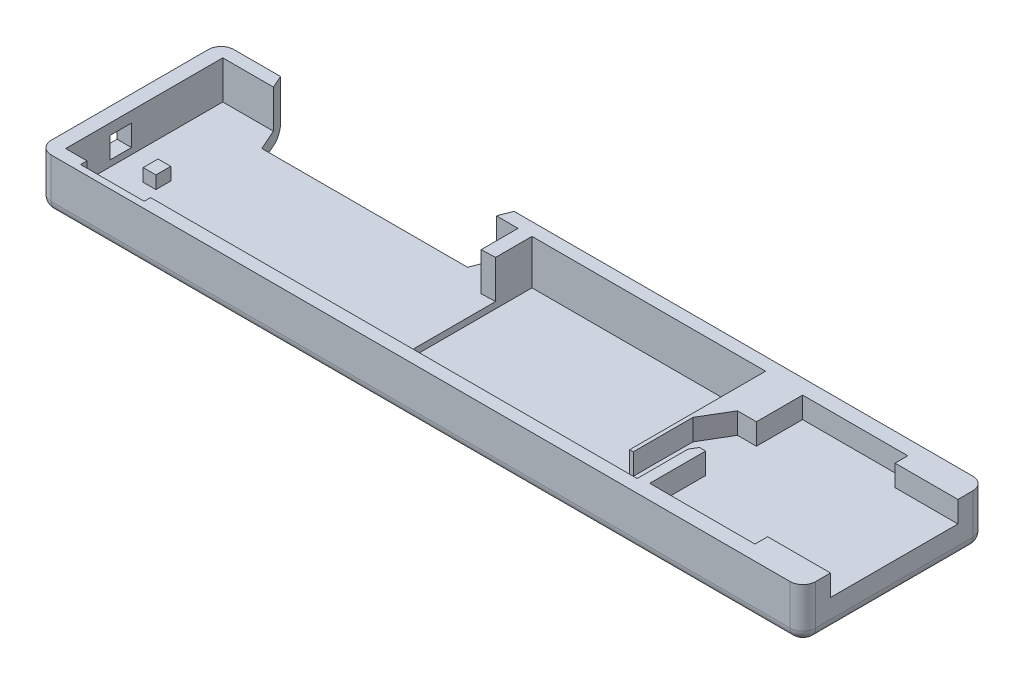
SolidWorks part; units mm, degrees
ref_plane "前视基准面" through (0, 0, 0) normal (0, 0, 1) x (1, 0, 0)
ref_plane "上视基准面" through (0, 0, 0) normal (0, 1, 0) x (1, 0, 0)
ref_plane "右视基准面" through (0, 0, 0) normal (1, 0, 0) x (0, 0, -1)
sketch "草图3" plane through (0, 0, 0) normal (0, 1, 0) x (1, 0, 0)
  line L1 (-39.9314, 29.2531) -> (140.0686, 29.2531)
  line L2 (-39.9314, 29.2531) -> (-39.9314, -13.7469)
  line L3 (-39.9314, -13.7469) -> (140.0686, -13.7469)
  line L4 (140.0686, 29.2531) -> (140.0686, -13.7469)
extrude "凸台-拉伸1" add sketch "草图3" along normal blind 12
sketch "草图4" plane through (0, 0, 0) normal (0, 1, 0) x (1, 0, 0)
  line L0 (-22.4696, -5.8589) -> (26.0023, -5.8589)
  line L1 (-39.9314, -13.7469) -> (140.0686, -13.7469) construction
  line L2 (-25.9314, -13.7469) -> (29.0686, -13.7469)
  line L5 (-25.9314, -13.7469) -> (-22.4696, -5.8589)
  line L6 (29.0686, -13.7469) -> (26.0023, -5.8589)
  point P11 (-22.4696, -5.8589)
  point P12 (26.0023, -5.8589)
extrude "切除-拉伸1" cut sketch "草图4" along normal blind 52
sketch "草图5" plane through (0, 12, 0) normal (0, 1, 0) x (1, 0, 0)
  line L6 (140.0686, -13.7469) -> (140.0686, 29.2531) construction
  line L7 (140.0686, 7.7531) -> (140.0686, 22.7531)
  line L8 (140.0686, 7.7531) -> (140.0686, -7.2469)
  line L9 (140.0686, 22.7531) -> (125.2765, 22.7531)
  line L10 (125.2765, 22.7531) -> (125.2765, -7.2469)
  line L11 (125.2765, -7.2469) -> (140.0686, -7.2469)
  point P0 (140.0686, 7.7531)
extrude "切除-拉伸2" cut sketch "草图5" against normal blind 5
sketch "草图7" plane through (0, 12, 0) normal (0, 1, 0) x (1, 0, 0)
  line L0 (125.2765, 22.7531) -> (125.2765, -7.2469) construction
  line L1 (125.2765, 7.7531) -> (125.2765, 25.7531)
  line L2 (125.2765, 7.7531) -> (125.2765, -10.2469)
  line L3 (125.2765, -10.2469) -> (100.5008, -10.2469)
  line L4 (100.5008, -10.2469) -> (100.5008, 25.7531)
  line L5 (100.5008, 25.7531) -> (125.2765, 25.7531)
  point P0 (125.2765, 7.7531)
extrude "切除-拉伸3" cut sketch "草图7" against normal blind 5
sketch "草图8" plane through (0, 12, 0) normal (0, 1, 0) x (1, 0, 0)
  line L1 (36.2763, 26.2531) -> (91.2763, 26.2531)
  line L2 (36.2763, 26.2531) -> (36.2763, -10.7469)
  line L3 (36.2763, -10.7469) -> (91.2763, -10.7469)
  line L4 (91.2763, 26.2531) -> (91.2763, -10.7469)
  line L6 (140.0686, 29.2531) -> (-39.9314, 29.2531) construction
  line L7 (29.0686, -13.7469) -> (140.0686, -13.7469) construction
  dimension "D1" = 3
  dimension "D2" = 3
extrude "切除-拉伸4" cut sketch "草图8" against normal blind 10.5
sketch "草图9" plane through (0, 12, 0) normal (0, 1, 0) x (1, 0, 0)
  line L0 (91.2763, -10.7469) -> (91.2763, 26.2531) construction
  line L1 (91.2763, 26.2531) -> (98.0396, 26.2531)
  line L2 (91.2763, 26.2531) -> (91.2763, 21.2551)
  line L4 (98.0396, 26.2531) -> (98.0396, 22.1306)
  line L5 (100.5008, 25.7531) -> (100.5008, -10.2469) construction
  line L7 (92.1327, 21.2551) -> (92.1327, 7.2269)
  line L12 (96.0473, 0.6296) -> (100.5008, 0.6296)
  line L13 (100.5008, 12.5794) -> (100.5008, 0.6296)
  line L14 (92.1327, 7.2269) -> (96.0473, 0.6296)
  line L15 (98.0396, 14.2797) -> (99.0486, 12.5794)
  line L17 (99.0486, 12.5794) -> (100.5008, 12.5794)
  line L19 (98.0396, 14.2797) -> (98.0396, 22.1306)
  line L20 (92.1327, 21.2551) -> (91.2763, 21.2551)
extrude "切除-拉伸5" cut sketch "草图9" against normal blind 5
sketch "草图10" plane through (0, 12, 0) normal (0, 1, 0) x (1, 0, 0)
  line L4 (-29.1302, -10.7469) -> (32.9986, -10.7469)
  line L5 (-29.1302, -10.7469) -> (-29.1302, -2.0631)
  line L6 (-29.1302, -2.0631) -> (32.9986, -2.0631)
  line L7 (32.9986, -10.7469) -> (32.9986, -2.0631)
extrude "切除-拉伸6" cut sketch "草图10" against normal blind 8
sketch "草图11" plane through (0, 12, 0) normal (0, 1, 0) x (1, 0, 0)
  line L0 (32.9986, -10.7469) -> (-36.5397, -10.7469)
  line L1 (36.2763, 26.2531) -> (36.2763, -10.7469) construction
  line L5 (-36.5397, 26.2531) -> (-36.5397, -10.7469)
  line L9 (36.2763, 26.2531) -> (36.2763, -2.1672)
  line L10 (-36.5397, 26.2531) -> (36.2763, 26.2531)
  line L11 (32.9986, -10.7469) -> (32.9986, -2.0631)
  line L12 (32.9986, -10.7469) -> (32.9986, -2.0631) construction
  line L13 (32.9986, -2.0631) -> (36.2763, -2.1672)
extrude "切除-拉伸8" cut sketch "草图11" against normal blind 9
fillet "圆角3" radius 3 4 edges at (140.0686, 6, -29.2531) (140.0686, 6, 13.7469) (-39.9314, 6, 13.7469) (-39.9314, 6, -29.2531)
fillet "圆角4" radius 2.5 9 edges at (50.0686, 0, -29.2531) (-39.0527, 0, 12.8682) (-31.4314, 0, 13.7469) (83.0686, 0, 13.7469) (139.1899, 0, 12.8682) (140.0686, 0, -7.7531) (139.1899, 0, -28.3744) (-39.0527, 0, -28.3744) (-39.9314, 0, -7.7531)
sketch "草图12" plane through (0, 12, 0) normal (0, 1, 0) x (1, 0, 0)
  line L0 (-36.5397, 26.2531) -> (-36.5397, -10.7469) construction
  line L1 (-16.5397, 26.2531) -> (-31.5397, 26.2531)
  line L2 (-16.5397, 26.2531) -> (-16.5397, 27.7531)
  line L3 (-16.5397, 27.7531) -> (-31.5397, 27.7531)
  line L4 (-31.5397, 26.2531) -> (-31.5397, 27.7531)
  dimension "D1" = 15
  dimension "D2" = 1.5
  dimension "D3" = 5
extrude "切除-拉伸9" cut sketch "草图12" against normal blind 5.5
sketch "草图14" plane through (-36.5397, 0, 0) normal (1, 0, 0) x (0, 0, -1)
  line L0 (26.2531, 12) -> (-10.7469, 12) construction
  line L1 (13.2531, 12) -> (13.2531, 9.45)
  line L2 (10.7531, 9.45) -> (15.7531, 9.45)
  line L3 (10.7531, 9.45) -> (10.7531, 4.45)
  line L4 (10.7531, 4.45) -> (15.7531, 4.45)
  line L5 (15.7531, 9.45) -> (15.7531, 4.45)
  line L6 (26.2531, 3) -> (-10.7469, 3) construction
  point P0 (13.2531, 12)
  point P8 (13.2531, 9.45)
  dimension "D1" = 13
  dimension "D2" = 1.45
  dimension "D3" = 5
  dimension "D4" = 5
extrude "切除-拉伸10" cut sketch "草图14" against normal blind 5.5 contours L5 L2 L3 L4 region at (-36.5397, 6.95, -13.2531)
sketch "草图15" plane through (0, 3, 0) normal (0, 1, 0) x (1, 0, 0)
  line L0 (36.2763, 26.2531) -> (-36.5397, 26.2531) construction
  line L1 (-29.5397, 15.0031) -> (-26.5397, 15.0031)
  line L2 (-29.5397, 15.0031) -> (-29.5397, 11.5031)
  line L3 (-29.5397, 11.5031) -> (-26.5397, 11.5031)
  line L4 (-26.5397, 15.0031) -> (-26.5397, 11.5031)
  line L5 (-36.5397, 26.2531) -> (-36.5397, -10.7469) construction
  point P4 (-29.5397, 13.2531)
  dimension "D1" = 13
  dimension "D2" = 7
  dimension "D3" = 3
  dimension "D4" = 3.5
extrude "凸台-拉伸2" add sketch "草图15" along normal blind 3
ref_plane "基准面1" through (0, 0, -39.2531) normal (0, 0, -1) x (-1, 0, 0)
mirror "镜向3" about plane through (0, 0, -39.2531) normal (0, 0, -1) of bodies 116
delete or keep bodies "实体-删除/保留 1" type delete bodies bodies 116
